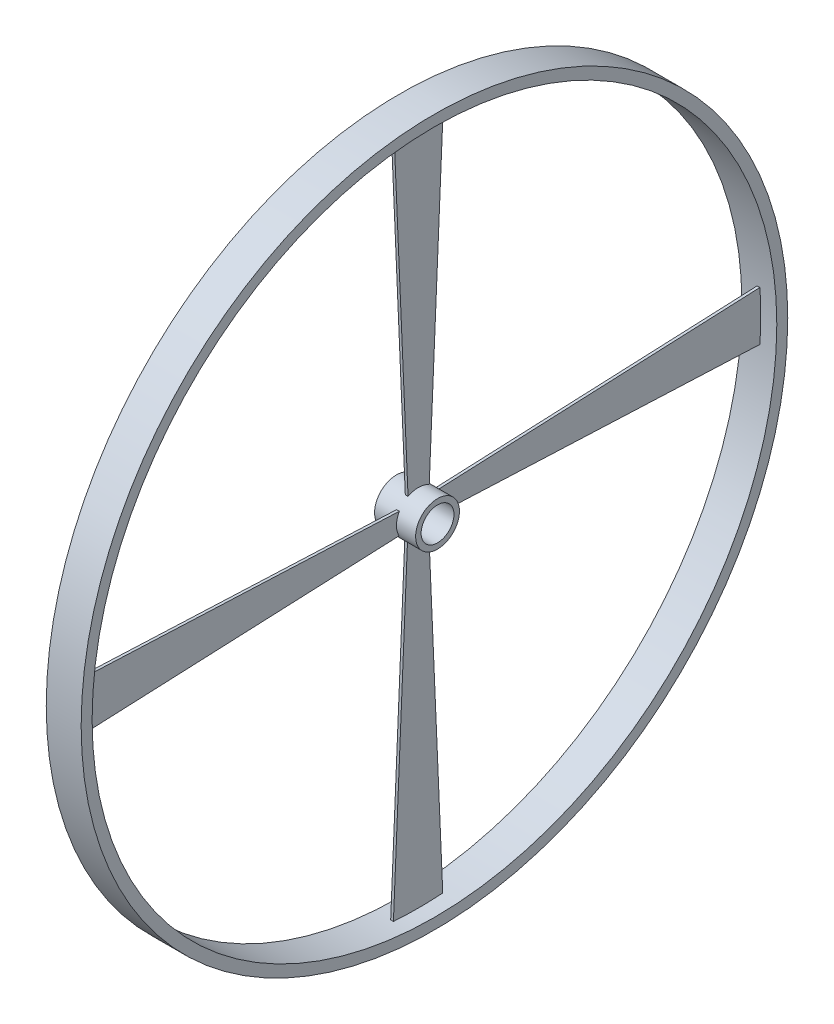
SolidWorks part; units mm, degrees
material "Malleable Cast Iron"
ref_plane "Front Plane" through (0, 0, 0) normal (0, 0, 1) x (1, 0, 0)
ref_plane "Top Plane" through (0, 0, 0) normal (0, 1, 0) x (1, 0, 0)
ref_plane "Right Plane" through (0, 0, 0) normal (1, 0, 0) x (0, 0, -1)
sketch "Sketch1" plane through (0, 0, 0) normal (1, 0, 0) x (0, 0, -1)
  circle A0 centre (0, 0) radius 129
  circle A1 centre (0, 0) radius 125
  dimension "D1" = 4
  dimension "D2" = 250
extrude "Boss-Extrude1" add sketch "Sketch1" along normal mid plane 12.75
sketch "Sketch2" plane through (0, 0, 0) normal (1, 0, 0) x (0, 0, -1)
  line L0 (3.9673, 6.947) -> (9.1071, 124.6678)
  line L1 (-3.7687, 7.0567) -> (-8.9044, 124.6824)
  line L2 (0, 0) -> (0, 125) construction
  line L3 (0, 0) -> (125, 0) construction
  line L4 (6.947, -3.9673) -> (124.6678, -9.1071)
  line L5 (7.0567, 3.7687) -> (124.6824, 8.9044)
  line L6 (-3.9673, -6.947) -> (-9.1071, -124.6678)
  line L7 (3.7687, -7.0567) -> (8.9044, -124.6824)
  line L8 (-6.947, 3.9673) -> (-124.6678, 9.1071)
  line L9 (-7.0567, -3.7687) -> (-124.6824, -8.9044)
  circle A0 centre (0, 0) radius 8
  circle A1 centre (0, 0) radius 125 construction
  circle A2 centre (0, 0) radius 125
  circle A3 centre (0, 0) radius 6
  point P28 (0, 0)
  dimension "D3" = 16
  dimension "D4" = 12
  dimension "D1" = 2.5
  dimension "D2" = 2.5
  dimension "D5" = 4
extrude "Boss-Extrude2" add sketch "Sketch2" along normal mid plane 1 contours L0 A2 L1 A0 | L8 A2 L9 A0 | L4 A2 L5 A0 | L6 A2 L7 A0 region at (0, 74.0255, -0.1017) region at (0, -0.1017, -74.0255) region at (0, 0.1017, 74.0255) region at (0, -74.0255, 0.1017)
extrude "Boss-Extrude3" add sketch "Sketch2<4>" along normal mid plane 15 contours A0 A3 region at (0, 5.4184, -5.5742)
sketch "Sketch2<4>" plane through (0, 0, 0) normal (1, 0, 0) x (0, 0, -1) same geometry as "Sketch2"
